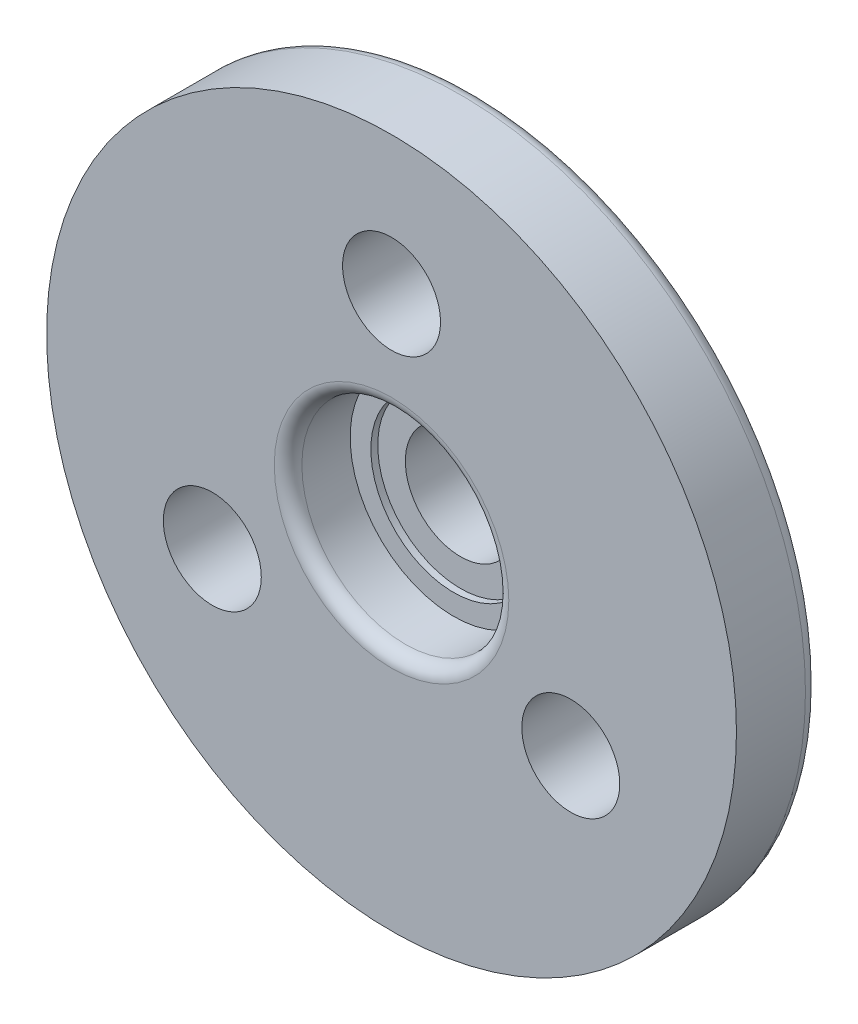
SolidWorks part; units mm, degrees
ref_plane "Ebene vorne" through (0, 0, 0) normal (0, 0, 1) x (1, 0, 0)
ref_plane "Ebene oben" through (0, 0, 0) normal (0, 1, 0) x (1, 0, 0)
ref_plane "Ebene rechts" through (0, 0, 0) normal (1, 0, 0) x (0, 0, -1)
sketch "Skizze2" plane through (0, 0, 0) normal (1, 0, 0) x (0, 0, -1)
  line L0 (0, 0) -> (99, 0) construction
  line L1 (9.5, 7) -> (8.5, 7) construction
  line L2 (9.5, 15) -> (9.5, 5) construction
  line L3 (18.5, 5) -> (9.5, 5) construction
  line L4 (18.5, 4) -> (18.5, 5) construction
  line L5 (18.5, 4) -> (7.5, 4) construction
  line L6 (7.5, 4) -> (7.5, 6) construction
  line L7 (7.5, 6) -> (7, 6) construction
  line L8 (7, 7.5) -> (7, 3) construction
  line L10 (7, 7.5) -> (2, 7.5) construction
  line L11 (2.5, 7.5) -> (2.5, 25) construction
  line L12 (8.5, 7) -> (8.5, 25) construction
  line L13 (0, 25) -> (99, 25) construction
  line L14 (0, 0) -> (99, 0) construction
  line L15 (9.5, 7) -> (8.5, 7)
  line L16 (9.5, 7) -> (9.5, 5)
  line L17 (18.5, 5) -> (9.5, 5)
  line L18 (18.5, 4) -> (18.5, 5)
  line L19 (18.5, 4) -> (7.5, 4)
  line L20 (7.5, 4) -> (7.5, 6)
  line L21 (7.5, 6) -> (7, 6)
  line L22 (7, 7.5) -> (7, 6)
  line L24 (7, 7.5) -> (2.5, 7.5)
  line L25 (2.5, 7.5) -> (2.5, 25)
  line L26 (8.5, 7) -> (8.5, 25)
  line L27 (2.5, 25) -> (8.5, 25)
revolve "Rotation1" add sketch "Skizze2" angle 360 about L14
sketch "Skizze3" plane through (0, 0, -2.5) normal (0, 0, 1) x (1, 0, 0)
  circle A0 centre (0, 0) radius 15 construction
  point P4 (0, 15)
hole_wizard "Ø7.1 (7.1) Durchmesser Bohrung1" positions "Skizze3" profile "Skizze4" hole size "Ø7.1" standard "DIN"
sketch "Skizze4" plane through (0, 15, -2.5) normal (1, 0, 0) x (0, -1, 0)
  line L0 (0, 0) -> (0, 11.6331)
  line L1 (0, 11.6331) -> (3.55, 9.5)
  line L2 (3.55, 9.5) -> (3.55, 0)
  line L5 (3.55, 0) -> (0, 0)
  line L10 (0, 11.6331) -> (-3.55, 9.5) construction
  line L11 (0, -6.35) -> (0, 107.95) construction
  dimension "Bohrerdurchmesser" = 7.1
  dimension "Bohrungstiefe" = 9.5
  dimension "Spitzenwinkel" = 118
pattern_circular "Kreismuster1" count 3 over 360 of "Ø7.1 (7.1) Durchmesser Bohrung1" reverse direction yes
fillet "Verrundung1" radius 1 3 edges at (5, 0, -18.5) (25, 0, -8.5) (7.5, 0, -2.5)
